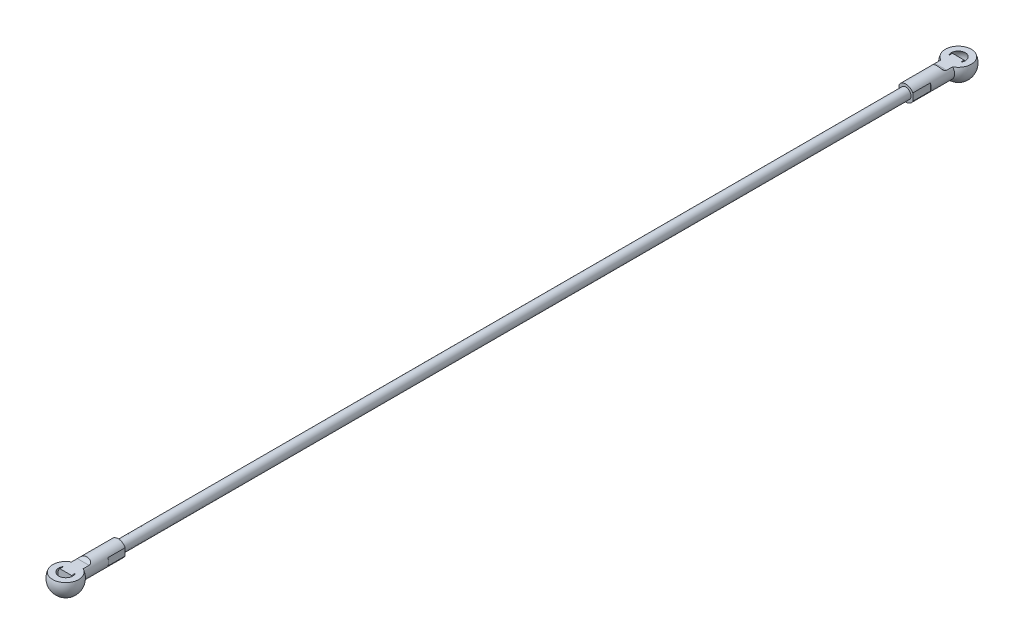
SolidWorks part; units mm, degrees
ref_plane "前视基准面" through (0, 0, 0) normal (0, 0, 1) x (1, 0, 0)
ref_plane "上视基准面" through (0, 0, 0) normal (0, 1, 0) x (1, 0, 0)
ref_plane "右视基准面" through (0, 0, 0) normal (1, 0, 0) x (0, 0, -1)
sketch "草图1" plane through (0, 0, 0) normal (0, 0, 1) x (1, 0, 0)
  line L0 (0, -1000) -> (0, 49000) construction
  line L1 (-7.4162, 3) -> (-4, 3)
  line L2 (0, -5) -> (0, -8)
  arc A0 (-4, 3) -> (0, -5) centre (0, 0) ccw
  arc A1 (-7.4162, 3) -> (0, -8) centre (0, 0) ccw
  dimension "D1" = 10
  dimension "D3" = 3
revolve "旋转4" add sketch "草图1" angle 360 about L0
sketch "草图2" plane through (0, 0, 0) normal (0, 0, 1) x (1, 0, 0)
  circle A0 centre (0, 0) radius 3
  dimension "D1" = 6
extrude "拉伸1" add sketch "草图2" along normal blind 510
sketch "草图4" plane through (0, 0, 0) normal (0, 0, 1) x (1, 0, 0)
  line L0 (0, -1000) -> (0, 49000) construction
  line L1 (0, -5) -> (0, 5)
  arc A0 (0, 5) -> (0, -5) centre (0, 0) ccw
revolve "切除-旋转1" cut sketch "草图4" angle 360 about L0
ref_plane "基准面1" through (0, 0, 510) normal (0, 0, 1) x (1, 0, 0)
sketch "草图6" plane through (0, 0, 510) normal (0, 0, 1) x (1, 0, 0)
  line L0 (-4, 3) -> (-7.4162, 3)
  line L1 (0, -1000) -> (0, 3) construction
  line L2 (0, -5) -> (0, -8)
  arc A0 (-7.4162, 3) -> (0, -8) centre (0, 0) ccw
  arc A1 (-4, 3) -> (0, -5) centre (0, 0) ccw
revolve "旋转6" add sketch "草图6" angle 360 about L1
sketch "草图7" plane through (0, 0, 0) normal (0, 0, 1) x (1, 0, 0)
  circle A0 centre (0, 0) radius 4.5
  dimension "D1" = 9
extrude "拉伸2" add sketch "草图7" along normal blind 30
sketch "草图8" plane through (0, 0, 0) normal (1, 0, 0) x (0, 0, -1)
  line L0 (7.4162, 3) -> (-10, 3)
  line L1 (0, 4.5) -> (7.4162, 3)
  line L2 (0, -1000) -> (0, 49000) construction
  line L3 (0, 4.5) -> (-30, 4.5) construction
  line L4 (0, 4.5) -> (-12.1024, 4.5)
  arc A0 (-12.1024, 4.5) -> (-10, 3) centre (-10, 5.2233) ccw
  dimension "D1" = 10
extrude "切除-拉伸1" cut sketch "草图8" against normal through all and the other way through all
sketch "草图9" plane through (0, 0, 510) normal (0, 0, 1) x (1, 0, 0)
  circle A1 centre (0, 0) radius 4.5
  circle A2 centre (0, 0) radius 4.5
  dimension "D1" = 0
extrude "拉伸3" add sketch "草图9" against normal blind 30
sketch "草图10" plane through (0, 0, 0) normal (1, 0, 0) x (0, 0, -1)
  line L0 (-522.2639, 3) -> (-500, 3)
  line L1 (-522.1884, 4.5) -> (-497.9082, 4.5)
  line L2 (-522.2639, 3) -> (-522.1884, 4.5)
  line L3 (-510, -996.4729) -> (-510, 49003.5271) construction
  arc A0 (-500, 3) -> (-497.9082, 4.5) centre (-500, 5.2085) ccw
  dimension "D1" = 10
extrude "切除-拉伸2" cut sketch "草图10" against normal blind 30 and the other way blind 30
sketch "草图11" plane through (0, 3, 0) normal (0, 1, 0) x (-1, 0, 0)
  line L0 (-4, 490) -> (-4, 475.1017)
  line L1 (-9.9257, 490) -> (-4, 490)
  line L2 (-9.9257, 490) -> (-9.9257, 475.1017)
  line L3 (-9.9257, 475.1017) -> (-4, 475.1017)
  line L4 (10.1397, 490) -> (10.1397, 475.1017)
  line L5 (4, 490) -> (10.1397, 490)
  line L6 (4, 490) -> (4, 475.1017)
  line L7 (4, 475.1017) -> (10.1397, 475.1017)
  line L8 (0, -492.1794) -> (0, 49507.8206) construction
  line L9 (-4.5, 507.8206) -> (4.5, 507.8206) construction
  line L10 (-4, 41.3823) -> (-4, 20)
  line L11 (-19.5787, 41.3823) -> (-4, 41.3823)
  line L12 (-19.5787, 41.3823) -> (-19.5787, 20)
  line L13 (-19.5787, 20) -> (-4, 20)
  line L14 (16.449, 41.3823) -> (16.449, 20)
  line L15 (4, 41.3823) -> (4, 20)
  line L16 (4, 41.3823) -> (16.449, 41.3823)
  line L17 (4, 20) -> (16.449, 20)
  line L18 (4.5, 30) -> (-4.5, 30) construction
  line L19 (-3, 480) -> (3, 480) construction
  point P13 (0, 507.8206)
  dimension "D1" = 4
  dimension "D2" = 8
  dimension "D3" = 10
  dimension "D4" = 10
  dimension "D5" = 4
  dimension "D6" = 8
extrude "切除-拉伸3" cut sketch "草图11" against normal blind 30 and the other way blind 30
